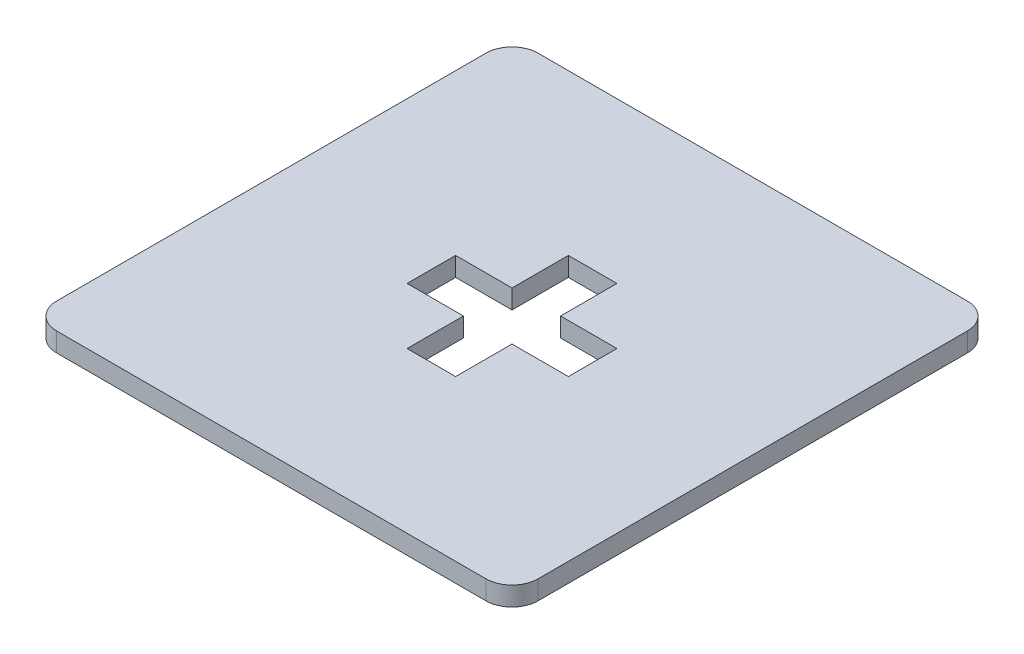
SolidWorks part; units mm, degrees
ref_plane "Plano frontal" through (0, 0, 0) normal (0, 0, 1) x (1, 0, 0)
ref_plane "Plano superior" through (0, 0, 0) normal (0, 1, 0) x (1, 0, 0)
ref_plane "Plano direito" through (0, 0, 0) normal (1, 0, 0) x (0, 0, -1)
sketch "Esboço1" plane through (0, 0, 0) normal (0, 1, 0) x (1, 0, 0)
  line L1 (-27.75, 27.75) -> (27.75, 27.75)
  line L2 (-27.75, 27.75) -> (-27.75, -27.75)
  line L3 (-27.75, -27.75) -> (27.75, -27.75)
  line L4 (27.75, 27.75) -> (27.75, -27.75)
  line L5 (-27.75, 27.75) -> (27.75, -27.75) construction
  line L6 (-27.75, -27.75) -> (27.75, 27.75) construction
  point P0 (0, 0)
  dimension "D1" = 55.5
  dimension "D2" = 55.5
extrude "Base" add sketch "Esboço1" along normal blind 2.2
sketch "Esboço3" plane through (0, 2.2, 0) normal (0, 1, 0) x (1, 0, 0)
  line L0 (0, 32.1703) -> (0, -31.3347) construction
  line L1 (-34.3986, 0) -> (42.476, 0) construction
  line L3 (-2.8, 9.3) -> (2.8, 9.3)
  line L4 (-2.8, 9.3) -> (-2.8, -9.3)
  line L5 (-2.8, -9.3) -> (2.8, -9.3)
  line L6 (2.8, 9.3) -> (2.8, -9.3)
  line L7 (-2.8, 9.3) -> (2.8, -9.3) construction
  line L8 (-2.8, -9.3) -> (2.8, 9.3) construction
  line L9 (-9.3, 2.8) -> (9.3, 2.8)
  line L10 (-9.3, 2.8) -> (-9.3, -2.8)
  line L11 (-9.3, -2.8) -> (9.3, -2.8)
  line L12 (9.3, 2.8) -> (9.3, -2.8)
  line L13 (-9.3, 2.8) -> (9.3, -2.8) construction
  line L14 (-9.3, -2.8) -> (9.3, 2.8) construction
  point P5 (0, 0)
  point P10 (0, 0)
  dimension "D1" = 5.6
  dimension "D2" = 18.6
  dimension "D3" = 5.6
  dimension "D4" = 18.6
extrude "Encaixe" cut sketch "Esboço3" against normal through all contours L4 L9 L6 L3 | L10 L11 L4 L9 | L11 L4 L5 L6 | L4 L11 L6 L9 | L12 L9 L6 L11 region at (0, 2.2, -6.05) region at (0, 2.2, 0) region at (-6.05, 2.2, 0) region at (6.05, 2.2, 0) region at (0, 2.2, 6.05)
fillet "Filetes dos cantos" radius 3 4 edges at (27.75, 1.1, -27.75) (27.75, 1.1, 27.75) (-27.75, 1.1, -27.75) (-27.75, 1.1, 27.75)
